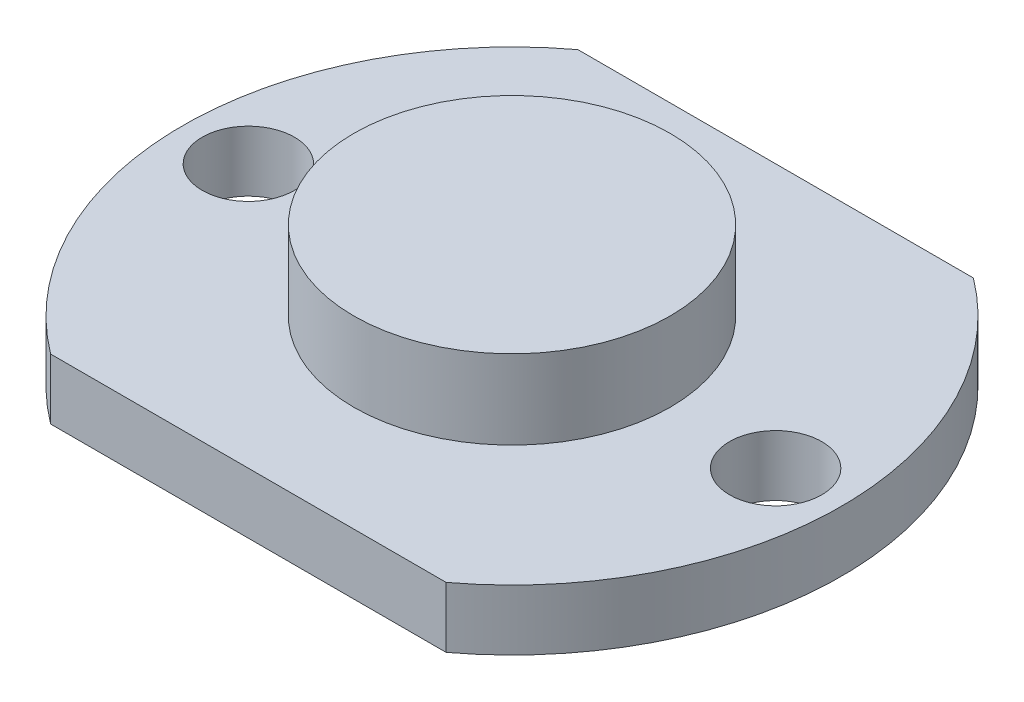
SolidWorks part; units mm, degrees
ref_plane "Front" through (0, 0, 0) normal (0, 0, 1) x (1, 0, 0)
ref_plane "Top" through (0, 0, 0) normal (0, 1, 0) x (1, 0, 0)
ref_plane "Right" through (0, 0, 0) normal (1, 0, 0) x (0, 0, -1)
sketch "Sketch1" plane through (0, 0, 0) normal (0, 1, 0) x (1, 0, 0)
  line L1 (7.5, -10) -> (-7.5, -10)
  line L3 (7.5, 10) -> (-7.5, 10)
  arc A0 (-7.5, 10) -> (-7.5, -10) centre (0, 0) ccw
  circle A1 centre (10, 0) radius 1.75
  circle A2 centre (-10, 0) radius 1.75
  arc A3 (7.5, -10) -> (7.5, 10) centre (0, 0) ccw
  dimension "D1" = 3.5
  dimension "D4" = 3.5
  dimension "D9" = 12.5
  dimension "D2" = 10
  dimension "D3" = 10
  dimension "D5" = 10
  dimension "D6" = 10
  dimension "D7" = 10
  dimension "D8" = 10
extrude "Boss-Extrude1" add sketch "Sketch1" along normal blind 2.3
sketch "Sketch3" plane through (0, 2.3, 0) normal (0, 1, 0) x (1, 0, 0)
  circle A0 centre (0, 0) radius 6
  dimension "D1" = 12
extrude "Boss-Extrude2" add sketch "Sketch3" along normal blind 3
